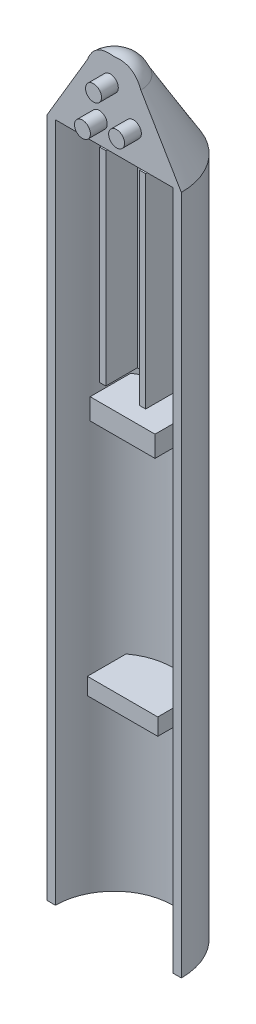
SolidWorks part; units mm, degrees
ref_plane "Front Plane" through (0, 0, 0) normal (0, 0, 1) x (1, 0, 0)
ref_plane "Top Plane" through (0, 0, 0) normal (0, 1, 0) x (1, 0, 0)
ref_plane "Right Plane" through (0, 0, 0) normal (1, 0, 0) x (0, 0, -1)
sketch "Sketch1" plane through (0, 0, 0) normal (0, 0, 1) x (1, 0, 0)
  line L0 (0, 91) -> (0, -91) construction
  line L1 (6.354, 87.279) -> (16, 71)
  line L2 (16, 71) -> (0, 71)
  line L3 (0, 91) -> (0, 71)
  spline S0 degree 2 poles (0, 91) (4.6686, 91.7236) (6.354, 87.279) knots 0 0 0 1 1 1
  point P3 (0, 0)
  dimension "D1" = 182
  dimension "D2" = 16
  dimension "D3" = 91
  dimension "D4" = 20
revolve "Revolve1" add sketch "Sketch1" angle 360 about L0
sketch "Sketch2" plane through (0, 0, 0) normal (0, 0, 1) x (1, 0, 0)
  line L0 (16, 71) -> (16, -91.0399)
  line L1 (16, -91.0399) -> (14, -91.0399)
  line L2 (14, -91.0399) -> (14, 71)
  line L3 (16, 71) -> (0, 71) construction
  line L4 (14, 71) -> (16, 71)
  dimension "D1" = 2
revolve "Revolve2" add sketch "Sketch2" angle 360 about L0
sketch "Sketch5" plane through (0, 0, 0) normal (0, 0, 1) x (1, 0, 0)
  line L1 (36.3918, -96.4232) -> (-36.3918, -96.4232)
  line L2 (36.3918, -96.4232) -> (36.3918, 96.4232)
  line L3 (36.3918, 96.4232) -> (-36.3918, 96.4232)
  line L4 (-36.3918, -96.4232) -> (-36.3918, 96.4232)
  line L5 (36.3918, -96.4232) -> (-36.3918, 96.4232) construction
  line L6 (36.3918, 96.4232) -> (-36.3918, -96.4232) construction
  point P0 (0, 0)
extrude "Cut-Extrude1" cut sketch "Sketch5" along normal through all
sketch "Sketch4" plane through (0, 0, 0) normal (0, 0, 1) x (1, 0, 0)
  line L0 (0, 91) -> (0, -91) construction
  line L5 (9, 7) -> (-9, 7)
  line L6 (9, 7) -> (9, -38)
  line L7 (9, -38) -> (-9, -38)
  line L8 (-9, 7) -> (-9, -38)
  line L9 (9, 7) -> (-9, -38) construction
  line L10 (9, -38) -> (-9, 7) construction
  line L11 (0, -100.299) -> (0, 100.299) construction
  line L12 (-7.7289, 11) -> (7.7289, 11)
  line L13 (-7.7289, 11) -> (-7.7289, 16)
  line L14 (-7.7289, 16) -> (7.7289, 16)
  line L15 (7.7289, 11) -> (7.7289, 16)
  line L16 (-7.7289, 11) -> (7.7289, 16) construction
  line L17 (-7.7289, 16) -> (7.7289, 11) construction
  line L18 (-8.3816, -46) -> (8.3816, -46)
  line L19 (-8.3816, -46) -> (-8.3816, -42)
  line L20 (-8.3816, -42) -> (8.3816, -42)
  line L21 (8.3816, -46) -> (8.3816, -42)
  line L22 (-8.3816, -46) -> (8.3816, -42) construction
  line L23 (-8.3816, -42) -> (8.3816, -46) construction
  line L24 (5.5, 20.0676) -> (4, 20.0676)
  line L25 (5.5, 20.0676) -> (5.5, 68.622)
  line L26 (5.5, 68.622) -> (4, 68.622)
  line L27 (4, 20.0676) -> (4, 68.622)
  line L28 (5.5, 20.0676) -> (4, 68.622) construction
  line L29 (5.5, 68.622) -> (4, 20.0676) construction
  line L30 (-5.5, 68.622) -> (-4, 20.0676) construction
  line L31 (-5.5, 20.0676) -> (-4, 68.622) construction
  line L32 (-4, 20.0676) -> (-4, 68.622)
  line L33 (-5.5, 68.622) -> (-4, 68.622)
  line L34 (-5.5, 20.0676) -> (-5.5, 68.622)
  line L35 (-5.5, 20.0676) -> (-4, 20.0676)
  line L36 (-4, 68.622) -> (4, 68.622)
  line L37 (-4, 20.0676) -> (4, 20.0676)
  point P0 (0, -15.5)
  point P1 (0, 13.5)
  point P12 (0, -44)
  point P17 (0, 16)
  point P19 (4.75, 44.3448)
  point P30 (-4.75, 44.3448)
  point P31 (0, -18.3141)
  point P32 (0, -44.9625)
  dimension "D1" = 45
  dimension "D2" = 4
  dimension "D3" = 55
  dimension "D4" = 1.5
  dimension "D5" = 4
  dimension "D6" = 4
  dimension "D7" = 5
  dimension "D8" = 18
  dimension "D9" = 4
extrude "Boss-Extrude1" add sketch "Sketch4" against normal up to next from offset 2 contours L12 L15 L14 L13 | L18 L21 L20 L19 | L27 L24 L25 L26 | L34 L35 L32 L33 region at (0, 13.5, 0) region at (0, -44, 0) region at (4.75, 44.3448, 0) region at (-4.75, 44.3448, 0) offset against normal yes
extrude "Boss-Extrude2" add sketch "Sketch4<4>" against normal up to next from offset 9.5 contours L32 L37 L27 L36 region at (0, 44.3448, 0) offset against normal yes
sketch "Sketch4<4>" plane through (0, 0, 0) normal (0, 0, 1) x (1, 0, 0) same geometry as "Sketch4"
sketch "Sketch6" plane through (0, 0, 0) normal (0, 0, 1) x (1, 0, 0)
  circle A0 centre (4.5793, 78.3675) radius 1.9
  circle A1 centre (-3.5585, 76.2554) radius 1.9
  circle A2 centre (-0.9193, 85.0766) radius 1.9
  dimension "D1" = 3.8
  dimension "D2" = 3.8
  dimension "D3" = 3.8
extrude "Boss-Extrude3" add sketch "Sketch6" along normal blind 4
